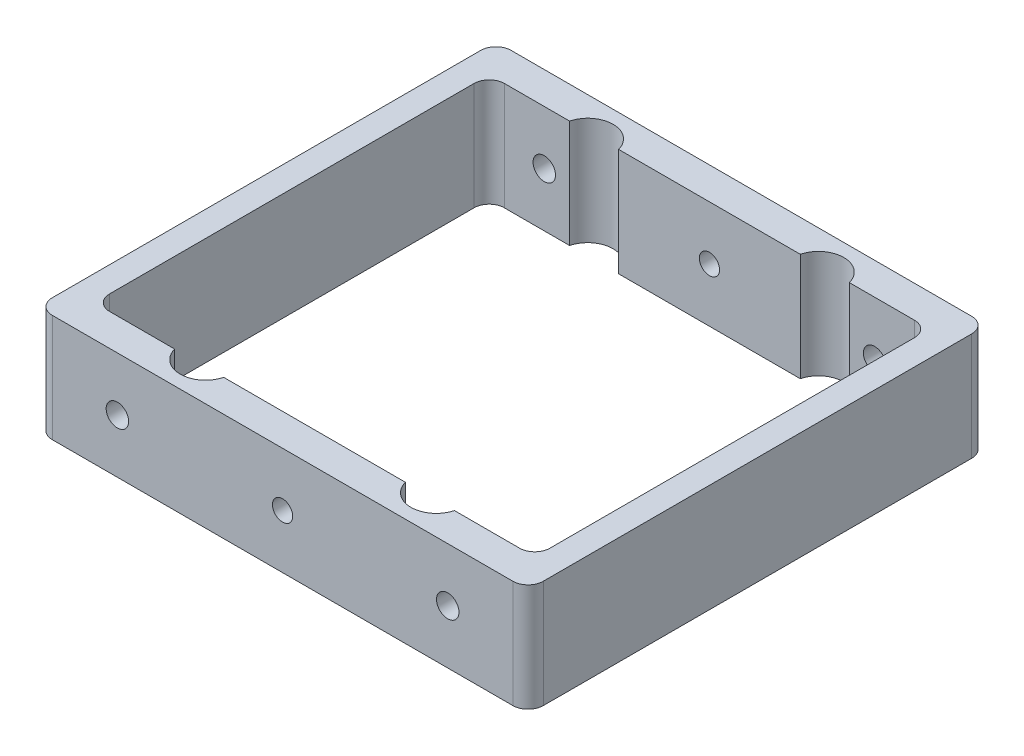
SolidWorks part; units mm, degrees
ref_plane "Front Plane" through (0, 0, 0) normal (0, 0, 1) x (1, 0, 0)
ref_plane "Top Plane" through (0, 0, 0) normal (0, 1, 0) x (1, 0, 0)
ref_plane "Right Plane" through (0, 0, 0) normal (1, 0, 0) x (0, 0, -1)
sketch "Sketch1" plane through (0, 0, 0) normal (0, 1, 0) x (1, 0, 0)
  line L1 (0, 0) -> (60, 0)
  line L2 (0, 0) -> (0, -6.32)
  line L3 (0, -6.32) -> (60, -6.32)
  line L4 (60, 0) -> (60, -6.32)
  dimension "D1" = 60
  dimension "D2" = 6.32
extrude "Boss-Extrude1" add sketch "Sketch1" along normal mid plane 21.28
sketch "Sketch2" plane through (0, 10.64, 0) normal (0, 1, 0) x (1, 0, 0)
  line L0 (0, 0) -> (0, -6.32) construction
  line L1 (0, -6.32) -> (60, -6.32) construction
  line L2 (60, -6.32) -> (60, 0) construction
  circle A0 centre (7.21, 1.25) radius 5
  circle A1 centre (52.79, 1.25) radius 5
  dimension "D1" = 7.21
  dimension "D3" = 7.21
  dimension "D2" = 7.57
  dimension "D4" = 7.57
extrude "Cut-Extrude1" cut sketch "Sketch2" against normal through all
sketch "Sketch3" plane through (60, 0, 0) normal (1, 0, 0) x (0, 0, -1)
  line L1 (-6.32, 10.64) -> (0, 10.64)
  line L2 (-6.32, 10.64) -> (-6.32, -10.64)
  line L3 (-6.32, -10.64) -> (0, -10.64)
  line L4 (0, 10.64) -> (0, -10.64)
extrude "Boss-Extrude2" add sketch "Sketch3" along normal blind 18.5
sketch "Sketch4" plane through (0, 0, 0) normal (-1, 0, 0) x (0, 0, 1)
  line L1 (0, 10.64) -> (6.32, 10.64)
  line L2 (0, 10.64) -> (0, -10.64)
  line L3 (0, -10.64) -> (6.32, -10.64)
  line L4 (6.32, 10.64) -> (6.32, -10.64)
extrude "Boss-Extrude3" add sketch "Sketch4" along normal blind 18.5
sketch "Sketch5" plane through (0, 0, 0) normal (0, 0, -1) x (-1, 0, 0)
  line L5 (-2.3688, -10.64) -> (18.5, -10.64) construction
  line L6 (18.5, 10.64) -> (13.5, 10.64)
  line L7 (18.5, 10.64) -> (18.5, -10.64)
  line L8 (18.5, -10.64) -> (13.5, -10.64)
  line L9 (13.5, 10.64) -> (13.5, -10.64)
  dimension "D1" = 5
extrude "Boss-Extrude6" add sketch "Sketch5" along normal blind 84.33
sketch "Sketch6" plane through (0, 0, 0) normal (0, 0, -1) x (-1, 0, 0)
  line L1 (-78.5, 10.64) -> (-73.5, 10.64)
  line L2 (-78.5, 10.64) -> (-78.5, -10.652)
  line L3 (-78.5, -10.652) -> (-73.5, -10.652)
  line L4 (-73.5, 10.64) -> (-73.5, -10.652)
  dimension "D1" = 5
extrude "Boss-Extrude7" add sketch "Sketch6" along normal blind 84.33
sketch "Sketch7" plane through (73.5, 0, 0) normal (-1, 0, 0) x (0, 0, 1)
  line L0 (-84.33, -10.652) -> (0, -10.652) construction
  line L1 (-84.33, 10.64) -> (-78.01, 10.64)
  line L2 (-84.33, 10.64) -> (-84.33, -10.652)
  line L3 (-84.33, -10.652) -> (-78.01, -10.652)
  line L4 (-78.01, 10.64) -> (-78.01, -10.652)
  dimension "D1" = 6.32
extrude "Boss-Extrude8" add sketch "Sketch7" along normal through all
sketch "Sketch9" plane through (0, 10.64, 0) normal (0, 1, 0) x (1, 0, 0)
  line L0 (-18.5, 84.33) -> (78.5, 84.33) construction
  circle A0 centre (7.21, 76.76) radius 5
  circle A1 centre (52.79, 76.76) radius 5
  dimension "D1" = 7.57
  dimension "D2" = 7.57
  dimension "D3" = 10
extrude "Cut-Extrude2" cut sketch "Sketch9" against normal through all
sketch "Sketch10" plane through (0, 0, -84.33) normal (0, 0, -1) x (-1, 0, 0)
  line L1 (-78.5, -10.64) -> (18.5, -10.64) construction
  line L2 (-30, -10.64) -> (-30, 10.64) construction
  line L3 (18.5, 10.64) -> (-78.5, 10.64) construction
  circle A0 centre (-62.6312, 0.005) radius 2.22
  circle A1 centre (2.6312, 0.005) radius 2.22
  dimension "D1" = 5
  dimension "D2" = 10.645
extrude "Cut-Extrude3" cut sketch "Sketch10" against normal through all
fillet "Fillet1" radius 3 8 edges at (-18.5, 0, 6.32) (78.5, 0, 6.32) (78.5, -0.006, -84.33) (-18.5, -0.006, -84.33) (-13.5, 0, -78.01) (-13.5, 0, 0) (73.5, -0.006, -78.01) (73.5, 0, 0)
sketch "Sketch13" plane through (0, 0, -84.33) normal (0, 0, -1) x (-1, 0, 0)
  line L1 (-75.5, 10.64) -> (-75.5, -10.652) construction
  line L2 (-75.5, -10.64) -> (15.5, -10.64) construction
  circle A0 centre (-30, 0.005) radius 2
  dimension "D1" = 45.5
  dimension "D2" = 10.645
extrude "Cut-Extrude4" cut sketch "Sketch13" against normal through all
sketch "Sketch16" plane through (0, -10.652, 0) normal (0, -1, 0) x (1, 0, 0)
  line L6 (75.5, -84.33) -> (-15.5, -84.33) construction
  line L7 (25.5729, -84.33) -> (12.6189, -84.33)
  line L8 (25.5729, -84.33) -> (25.5729, -78.01)
  line L9 (25.5729, -78.01) -> (12.6189, -78.01)
  line L10 (12.6189, -84.33) -> (12.6189, -78.01)
  line L11 (12.0512, -78.01) -> (47.9488, -78.01) construction
  point P4 (25.3853, -84.33)
  point P7 (25.9282, -78.01)
  dimension "D1" = 12.954
extrude "Cut-Extrude6" [suppressed] cut sketch "Sketch16" against normal mid plane 25.4
